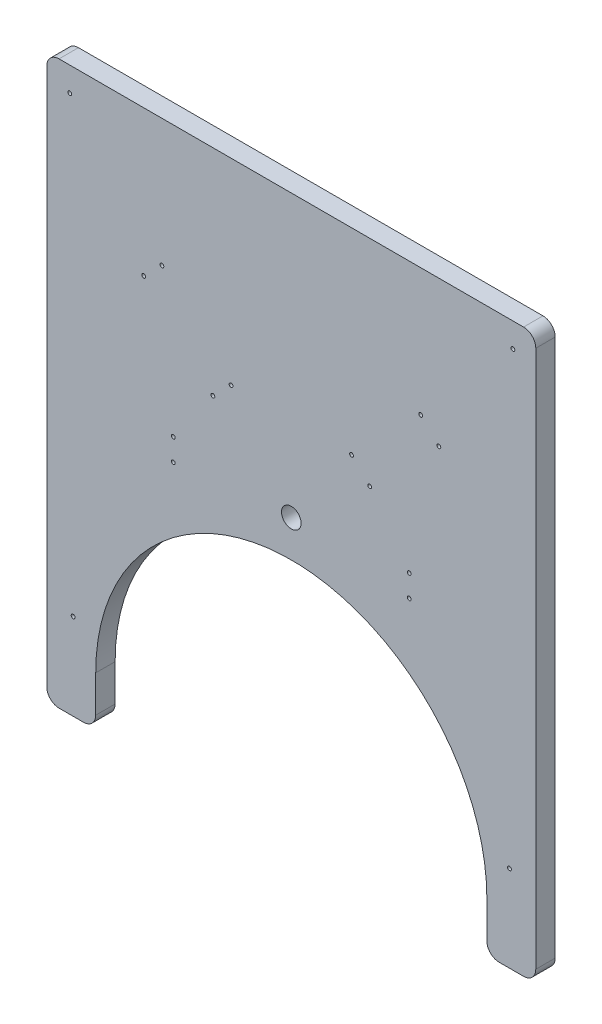
SolidWorks part; units mm, degrees
ref_plane "Front Plane" through (0, 0, 0) normal (0, 0, 1) x (1, 0, 0)
ref_plane "Top Plane" through (0, 0, 0) normal (0, 1, 0) x (1, 0, 0)
ref_plane "Right Plane" through (0, 0, 0) normal (1, 0, 0) x (0, 0, -1)
sketch "Sketch1" plane through (0, 0, 0) normal (0, 0, 1) x (1, 0, 0)
  line L1 (-200, 230) -> (200, 230)
  line L2 (-200, 230) -> (-200, -230)
  line L3 (-200, -230) -> (200, -230)
  line L4 (200, 230) -> (200, -230)
  line L5 (-200, 230) -> (200, -230) construction
  line L6 (-200, -230) -> (200, 230) construction
  point P0 (0, 0)
  dimension "D1" = 400
  dimension "D2" = 460
extrude "Boss-Extrude1" add sketch "Sketch1" against normal blind 15.875
sketch "Sketch2" plane through (0, 0, 0) normal (0, 0, 1) x (1, 0, 0)
  line L0 (160, -230) -> (160, -190)
  line L1 (-200, -230) -> (200, -230) construction
  line L2 (-160, -230) -> (-160, -190)
  line L3 (-160, -230) -> (160, -230)
  line L4 (200, -230) -> (200, 230) construction
  arc A0 (160, -190) -> (-160, -190) centre (0, -190) ccw
  dimension "D2" = 40
  dimension "D1" = 40
extrude "Cut-Extrude1" cut sketch "Sketch2" against normal through all
fillet "Fillet1" radius 10 6 edges at (-160, -230, -7.9375) (-200, -230, -7.9375) (160, -230, -7.9375) (200, -230, -7.9375) (-200, 230, -7.9375) (200, 230, -7.9375)
sketch "Sketch3" plane through (0, 0, 0) normal (0, 0, 1) x (1, 0, 0)
  line L0 (190, 230) -> (-190, 230) construction
  circle A0 centre (0, 0) radius 8
  dimension "D2" = 16
  dimension "D1" = 230
extrude "Cut-Extrude2" cut sketch "Sketch3" against normal through all
sketch "Sketch4" plane through (0, 0, 0) normal (0, 0, 1) x (1, 0, 0)
  point P0 (181.2487, 210.112)
  point P1 (-181.2487, 210.112)
  point P3 (-178.461, -159.2706)
  point P5 (178.461, -159.2706)
sketch "Sketch5" plane through (0, 0, 0) normal (0, 0, 1) x (1, 0, 0)
  line L0 (-200, 220) -> (-200, -220) construction
  line L1 (190, 230) -> (-190, 230) construction
  circle A1 centre (-181.2487, 210.112) radius 1.5875
  circle A3 centre (-178.461, -159.2706) radius 1.5875
  dimension "D5" = 3.175
  dimension "D1" = 21.539
  dimension "D2" = 389.2706
  dimension "D3" = 18.7513
  dimension "D4" = 19.888
extrude "Cut-Extrude3" cut sketch "Sketch5" against normal through all
mirror "Mirror1" about plane through (0, 0, 0) normal (1, 0, 0) of "Cut-Extrude3"
sketch "Sketch6" plane through (0, 0, 0) normal (0, 0, 1) x (1, 0, 0)
  circle A0 centre (-96.5, 9) radius 1.5625
  circle A1 centre (-96.5, -9) radius 1.5625
  circle A2 centre (96.5, 9) radius 1.5625
  circle A3 centre (96.5, -9) radius 1.5625
  dimension "D1" = 3.125
extrude "Cut-Extrude4" cut sketch "Sketch6" against normal through all
sketch "Sketch7" plane through (0, 0, 0) normal (0, 0, 1) x (1, 0, 0)
  circle A0 centre (-49.2911, 69.1403) radius 1.5625
  circle A1 centre (-64.1403, 54.2911) radius 1.5625
  circle A2 centre (-105.8597, 125.7089) radius 1.5625
  circle A3 centre (-120.7089, 110.8597) radius 1.5625
  circle A4 centre (105.8597, 125.7089) radius 1.5625
  circle A5 centre (120.7089, 110.8597) radius 1.5625
  circle A6 centre (49.2911, 69.1403) radius 1.5625
  circle A7 centre (64.1403, 54.2911) radius 1.5625
  dimension "D1" = 3.125
extrude "Cut-Extrude5" cut sketch "Sketch7" against normal through all
